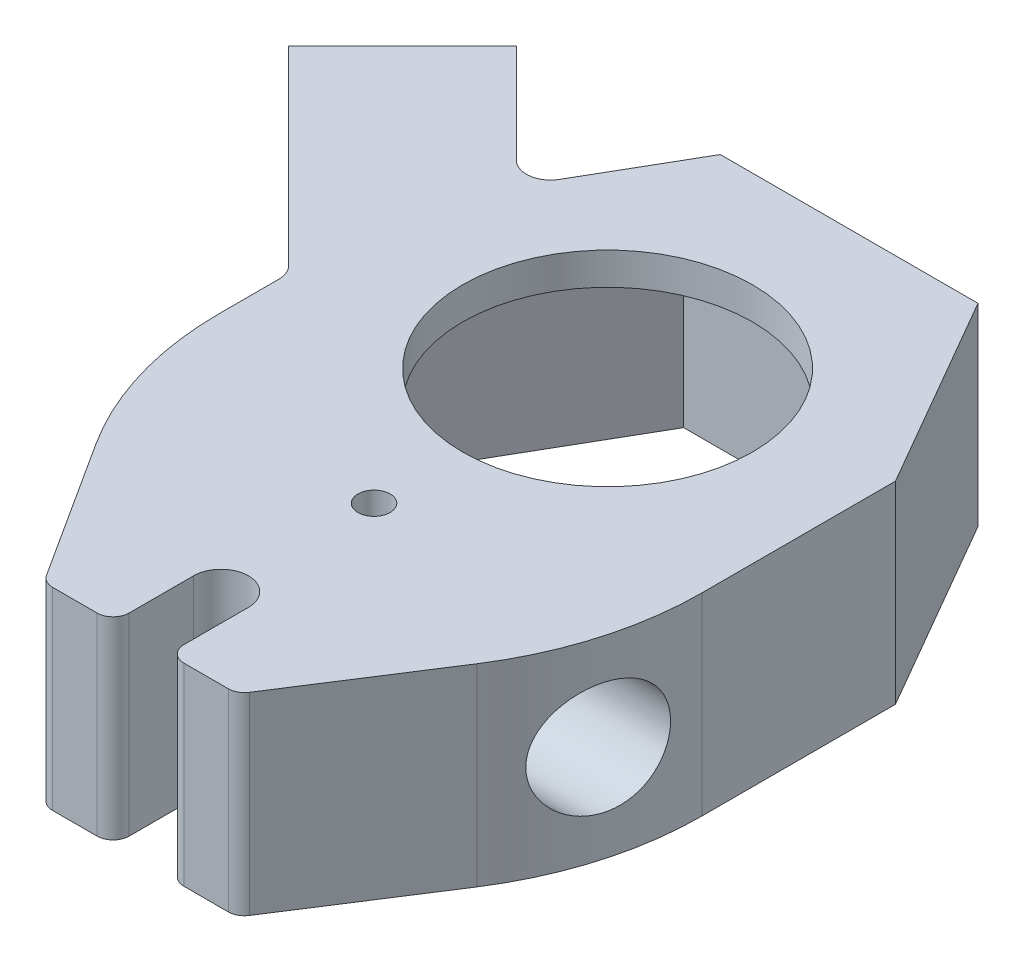
SolidWorks part; units mm, degrees
note: '?' marks a value the reader was unsure of.
ref_plane "Front Plane" through (0, 0, 0) normal (0, 0, 1) x (1, 0, 0)
ref_plane "Top Plane" through (0, 0, 0) normal (0, 1, 0) x (1, 0, 0)
ref_plane "Right Plane" through (0, 0, 0) normal (1, 0, 0) x (0, 0, -1)
ref_axis "Axis1" through (0, 14.8656, 0) along (0, -1, 0)?
sketch "Sketch1" plane through (0, 0, 0) normal (0, 1, 0) x (1, 0, 0)
  line L0 (0, 15) -> (0, -15) construction
  line L5 (-15, 15) -> (15, 15)
  line L7 (-15, 15) -> (-15, -15)
  line L10 (-15, -15) -> (15, -15)
  line L11 (15, 15) -> (15, -15)
  line L13 (6.4525, -11.176) -> (12.9049, 0)
  line L14 (12.9049, 0) -> (6.4525, 11.176)
  line L15 (6.4525, 11.176) -> (-6.4525, 11.176)
  line L16 (-6.4525, 11.176) -> (-12.9049, 0)
  line L17 (-12.9049, 0) -> (-6.4525, -11.176)
  line L18 (-6.4525, -11.176) -> (6.4525, -11.176)
  circle A0 centre (0, 0) radius 11.176 construction
  dimension "D3" = 15
  dimension "D4" = 22.352
  dimension "D1" = 30
  dimension "D2" = 30
extrude "Boss-Extrude1" add sketch "Sketch1" along normal blind 12
sketch "Sketch8" plane through (0, 0, 0) normal (0, 1, 0) x (1, 0, 0)
  line L0 (-15, -15) -> (15, -15) construction
  line L1 (-6, -15) -> (6, -15)
  line L2 (-6, -15) -> (-6, -29)
  line L3 (-6, -29) -> (-1.7, -29)
  line L4 (6, -15) -> (6, -29)
  line L5 (0, 0) -> (0, -30) construction
  line L6 (-1.7, -24) -> (-1.7, -29)
  line L7 (1.7, -24) -> (1.7, -29)
  line L8 (1.7, -29) -> (6, -29)
  arc A0 (1.7, -24) -> (-1.7, -24) centre (0, -24) ccw
  dimension "D2" = 3.4
  dimension "D1" = 24
  dimension "D3" = 5
  dimension "D4" = 12
extrude "Boss-Extrude6" add sketch "Sketch8" along normal up to surface (12 mm away) up to face at (0, 12, 0)
sketch "Sketch9" plane through (0, 12, 0) normal (0, 1, 0) x (1, 0, 0)
  line L27 (-14.637, 0) -> (-7.3185, -12.676)
  line L28 (-7.3185, -12.676) -> (7.3185, -12.676)
  line L29 (7.3185, -12.676) -> (14.637, 0)
  line L30 (14.637, 0) -> (7.3185, 12.676)
  line L31 (7.3185, 12.676) -> (-7.3185, 12.676)
  line L32 (-7.3185, 12.676) -> (-14.637, 0)
  line L33 (-14.637, 0) -> (-7.3185, -12.676)
  line L34 (-7.3185, -12.676) -> (7.3185, -12.676)
  line L35 (7.3185, -12.676) -> (14.637, 0)
  line L36 (14.637, 0) -> (7.3185, 12.676)
  line L37 (7.3185, 12.676) -> (-7.3185, 12.676)
  line L38 (-7.3185, 12.676) -> (-14.637, 0)
  circle A0 centre (0, 0) radius 9
  dimension "D2" = 18
  dimension "D1" = 1.5
extrude "Boss-Extrude7" [suppressed] add sketch "Sketch9" along normal blind 2
sketch "Sketch3" plane through (0, 12, 0) normal (0, 1, 0) x (1, 0, 0)
  line L1 (-5.25, -18.5) -> (5.25, -18.5)
  line L2 (-5.25, -18.5) -> (-5.25, -10.5)
  line L3 (-5.25, -10.5) -> (5.25, -10.5)
  line L4 (5.25, -18.5) -> (5.25, -10.5)
  line L5 (0, 0) -> (0, -30) construction
  line L6 (-5.25, -14.5) -> (5.25, -14.5) construction
  circle A0 centre (0, -14.5) radius 1
  dimension "D3" = 2
  dimension "D1" = 8
  dimension "D2" = 10.5
  dimension "D4" = 14.5
extrude "Boss-Extrude3" [suppressed] add sketch "Sketch3" along normal blind 10
sketch "Sketch5" [suppressed] plane through (5.25, 0, 0) normal (1, 0, 0) x (0, 0, -1)
  line L0 (-14.5, 20) -> (-14.5, 10) construction
  line L1 (-18.5, 20) -> (-10.5, 20) construction
  line L4 (-15, 10) -> (15, 10) construction
  circle A0 centre (-14.5, 15) radius 2
  dimension "D1" = 4
extrude "Cut-Extrude1" [suppressed] cut sketch "Sketch5" against normal blind 5
chamfer "Chamfer1" distance 7 angle 60 2 edges at (-15, 6, -15) (15, 6, -15)
sketch "Sketch6" plane through (0, 0, 0) normal (0, 1, 0) x (1, 0, 0)
  line L0 (0, 0) -> (0, -19.1236) construction
  line L1 (0, 0) -> (-11.2123, 11.2123) construction
  line L11 (-11.2123, 11.2123) -> (-21.1118, 1.3128) construction
  line L12 (-27.2236, 7.4246) -> (-15, -4.799)
  line L13 (-27.2236, 7.4246) -> (-20.1525, 14.4957)
  line L14 (-20.1525, 14.4957) -> (-12.6327, 6.9759)
  line L18 (-8, 15) -> (-15, 2.8756) construction
  line L19 (-15, 2.8756) -> (-15, -15) construction
  line L20 (-15, -4.799) -> (-15, 2.8756)
  line L21 (-15, 2.8756) -> (-12.6327, 6.9759)
  dimension "D1" = 45
  dimension "D3" = 24.5
  dimension "D4" = 10
  dimension "D5" = 14
extrude "Boss-Extrude4" add sketch "Sketch6" along normal up to surface (12 mm away) up to face at (0, 12, 13.3249)
sketch "Sketch7" plane through (-9.8995, 0, 9.8995) normal (-0.7071, 0, 0.7071) x (0.7071, 0, 0.7071)
  line L0 (-19.5, 12) -> (-19.5, 0) construction
  line L1 (-7.2132, 12) -> (-24.5, 12) construction
  line L2 (-7.2132, 0) -> (-24.5, 0) construction
  line L3 (-24.5, 12) -> (-24.5, 0) construction
  circle A0 centre (-19.5, 6) radius 2.8
  dimension "D1" = 5.6
  dimension "D2" = 5
extrude "Cut-Extrude2" cut sketch "Sketch7" against normal blind 15
chamfer "Chamfer2" distance 14 distance2 9 1 edges at (6, 6, 15)
chamfer "Chamfer3" distance 9 distance2 14 1 edges at (-6, 6, 15)
fillet "Fillet2" radius 20 2 edges at (-15, 6, 15) (15, 6, 15)
fillet "Fillet3" radius 1 4 edges at (1.7, 6, 29) (-1.7, 6, 29) (6, 6, 29) (-6, 6, 29)
draft "Draft1" [suppressed] type of draft neutral plane draft angle 10 faces to draft 2 parameters "D1"=10
draft "Draft2" [suppressed] type of draft neutral plane draft angle 5 faces to draft 7 parameters "D1"=5
fillet "Fillet4" radius 1.5 2 edges at (-12.6327, 6, -6.9759) (-15, 6, 4.799)
sketch "Sketch10" plane through (0, 12, 0) normal (0, 1, 0) x (1, 0, 0)
  circle A0 centre (0, -14.5) radius 1
  dimension "D2" = 2
  dimension "D1" = 14.5
extrude "Cut-Extrude3" cut sketch "Sketch10" against normal through all
sketch "Sketch11" plane through (0, 0, 0) normal (1, 0, 0) x (0, 0, -1)
  line L0 (-13.5, 12) -> (-15.5, 12) construction
  line L1 (-13.5, 12) -> (-15.5, 12) construction
  line L2 (-15.5, 0) -> (-13.5, 0) construction
  line L3 (-15.5, 0) -> (-13.5, 0) construction
  line L4 (-14.5, 12) -> (-14.5, 0) construction
  circle A0 centre (-14.5, 6) radius 2
  dimension "D1" = 4
extrude "Cut-Extrude4" cut sketch "Sketch11" along normal through all
sketch "Sketch12" plane through (0, 12, 0) normal (0, 1, 0) x (1, 0, 0)
  line L0 (6.4525, 11.176) -> (-6.4525, 11.176) construction
  line L1 (12.9049, 0) -> (6.4525, 11.176) construction
  line L2 (6.4525, -11.176) -> (12.9049, 0) construction
  line L3 (-6.4525, -11.176) -> (6.4525, -11.176) construction
  line L4 (-12.9049, 0) -> (-6.4525, -11.176) construction
  line L5 (-6.4525, 11.176) -> (-12.9049, 0) construction
  line L6 (6.4525, 11.176) -> (-6.4525, 11.176)
  line L7 (12.9049, 0) -> (6.4525, 11.176)
  line L8 (6.4525, -11.176) -> (12.9049, 0)
  line L9 (-6.4525, -11.176) -> (6.4525, -11.176)
  line L10 (-12.9049, 0) -> (-6.4525, -11.176)
  line L11 (-6.4525, 11.176) -> (-12.9049, 0)
  circle A0 centre (0, 0) radius 9
  dimension "D1" = 18
extrude "Boss-Extrude8" add sketch "Sketch12" against normal offset from surface (2 mm away) 10 up to face at (0, 0, 15.5)
sketch "Sketch13" plane through (15, 0, 0) normal (1, 0, 0) x (0, 0, -1)
  circle A0 centre (-14.5, 6) radius 3.5
  dimension "D1" = 7
extrude "Cut-Extrude5" cut sketch "Sketch13" against normal blind 8
